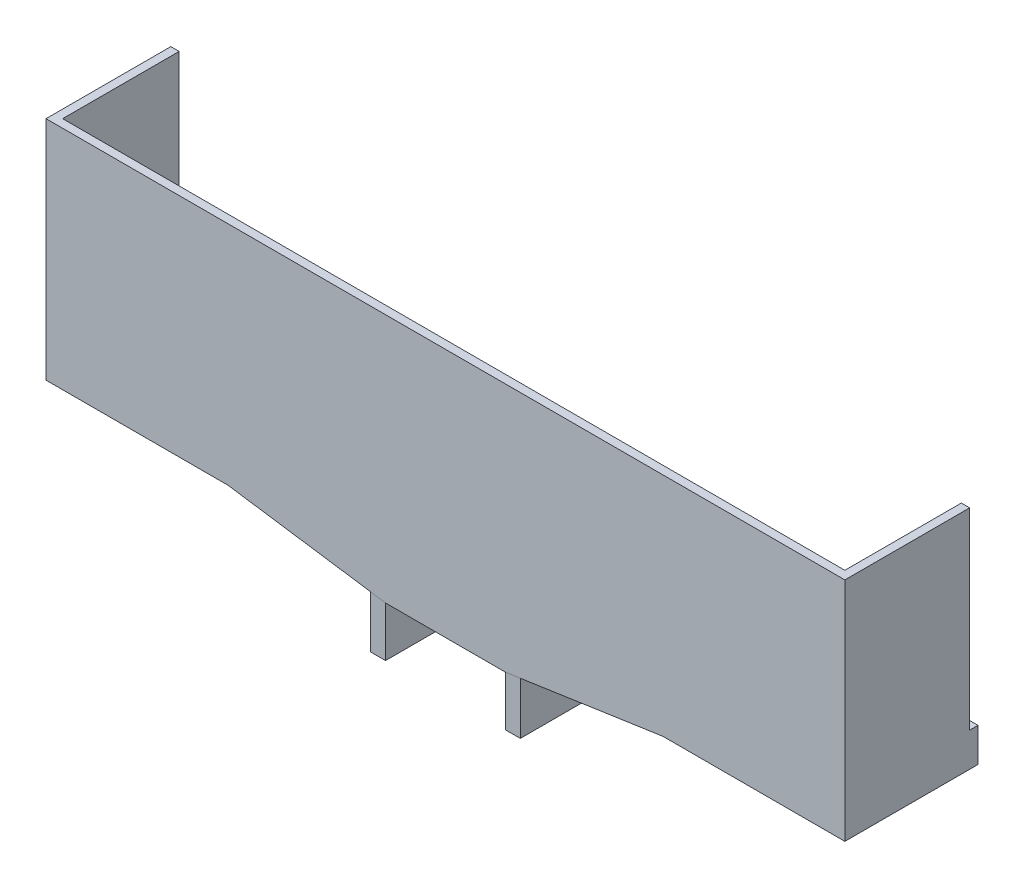
SolidWorks part; units mm, degrees
ref_plane "前基準面" through (0, 0, 0) normal (0, 0, 1) x (1, 0, 0)
ref_plane "上基準面" through (0, 0, 0) normal (0, 1, 0) x (1, 0, 0)
ref_plane "右基準面" through (0, 0, 0) normal (1, 0, 0) x (0, 0, -1)
sketch "草圖20" plane through (0, 0, 0) normal (0, 0, 1) x (1, 0, 0)
  line L0 (-36, 0) -> (36, 0) construction
  line L1 (-36, 0) -> (-240, 30)
  line L2 (-240, 30) -> (240, 30) construction
  line L3 (240, 30) -> (36, 0)
  line L4 (36, 0) -> (-36, 0)
  line L5 (0, 89.4424) -> (0, -40.7257) construction
  line L7 (-240, 30) -> (240, 30) construction
  line L8 (-240, 30) -> (-240, 150)
  line L9 (-240, 150) -> (240, 150)
  line L10 (240, 30) -> (240, 150)
  point P2 (0, 0)
  dimension "D1" = 72
  dimension "D2" = 480
  dimension "D3" = 30
  dimension "D4" = 120
extrude "填料-伸長1" add sketch "草圖20" along normal blind 80
ref_plane "平面1" through (0, 0, 5) normal (0, 0, 1) x (1, 0, 0)
sketch "草圖22" plane through (0, 0, 5) normal (0, 0, 1) x (1, 0, 0)
  line L6 (-235, 34.3185) -> (-35.6343, 5)
  line L7 (-235, 34.3185) -> (-36, 5.0538)
  line L8 (35.6343, 5) -> (235, 34.3185)
  line L9 (36, 5.0538) -> (235, 34.3185)
  line L332 (36, 0) -> (36, 5.0538)
  line L333 (-36, 0) -> (-36, 5.0538)
  line L334 (-36, 0) -> (36, 0) construction
  line L335 (-36, 0) -> (36, 0)
  line L336 (240, 150) -> (-240, 150) construction
  line L337 (235, 150) -> (-235, 150)
  line L338 (-35.6343, 5) -> (35.6343, 5)
  line L340 (-235, 145) -> (-235, 34.3185)
  line L341 (235, 145) -> (-235, 145)
  line L342 (235, 34.3185) -> (235, 145)
  line L346 (-235, 150) -> (-235, 34.3185)
  line L348 (235, 34.3185) -> (235, 150)
  dimension "D1" = 5
extrude "除料-伸長1" cut sketch "草圖22" along normal blind 70
sketch "草圖23" plane through (0, 0, 0) normal (0, 0, -1) x (-1, 0, 0)
  line L0 (-240, 34.3185) -> (-235, 34.3185)
  line L1 (-240, 150) -> (240, 150)
  line L2 (-240, 150) -> (-240, 34.3185)
  line L4 (240, 150) -> (240, 34.3185)
  line L5 (240, 150) -> (240, 30) construction
  line L6 (235, 34.3185) -> (36, 5.0538) construction
  line L7 (-36, 5.0538) -> (-235, 34.3185) construction
  line L8 (235, 34.3185) -> (36, 5.0538)
  line L9 (-36, 5.0538) -> (-235, 34.3185)
  line L10 (235, 34.3185) -> (240, 34.3185)
  line L15 (-36, 0) -> (36, 0)
  line L16 (-36, 5.0538) -> (-36, 0)
  line L17 (-235, 34.3185) -> (-36, 5.0538)
  line L18 (-235, 150) -> (-235, 34.3185)
  line L19 (235, 150) -> (-235, 150)
  line L20 (235, 34.3185) -> (235, 150)
  line L21 (36, 5.0538) -> (235, 34.3185)
  line L22 (36, 0) -> (36, 5.0538)
  line L23 (-36, 0) -> (36, 0)
  line L24 (-36, 5.0538) -> (-36, 0)
  line L25 (-235, 34.3185) -> (-36, 5.0538) construction
  line L26 (-235, 150) -> (-235, 34.3185) construction
  line L27 (235, 150) -> (-235, 150) construction
  line L28 (235, 34.3185) -> (235, 150) construction
  line L29 (36, 5.0538) -> (235, 34.3185) construction
  line L30 (36, 0) -> (36, 5.0538)
  dimension "D1" = 0
extrude "除料-伸長2" cut sketch "草圖23" against normal up to surface (5 mm away) up to face at (0, 47.3431, 5)
sketch "草圖25" plane through (0, 0, 0) normal (0, -1, 0) x (1, 0, 0)
  line L0 (-240, 80) -> (-36, 80) construction
  line L1 (-45, 80) -> (-36, 80)
  line L2 (-45, 80) -> (-45, 40)
  line L3 (-45, 40) -> (-36, 40)
  line L4 (45, 80) -> (45, 40)
  line L8 (-36, 75) -> (-36, 0) construction
  line L9 (-36, 75) -> (-36, 0)
  line L10 (36, 75) -> (36, 0) construction
  line L11 (36, 75) -> (36, 0)
  line L14 (0, 112.0403) -> (0, -32.5908) construction
  line L15 (-36, 80) -> (-36, 40)
  line L16 (36, 80) -> (45, 80)
  line L17 (36, 80) -> (36, 40)
  line L18 (36, 40) -> (45, 40)
  point P20 (0, 0)
  point P22 (0, 0)
  point P25 (0, 0)
  point P26 (0, 0)
  line M10 (-36, 80) -> (-36, 75)
  line M12 (36, 75) -> (36, 80)
  dimension "D1" = 90
  dimension "D2" = 40
extrude "填料-伸長3" add sketch "草圖25" along normal blind 30 and the other way up to next separate body contours L15 L9 L1 L2 L3 M10 | L17 L18 L4 L16 L11 M12 region at (-40.5, 0, 60) region at (40.5, 0, 60)
sketch "草圖26" plane through (0, 0, 0) normal (0, 0, -1) x (-1, 0, 0)
  line L0 (-130.69, 13.925) -> (-240, 13.925)
  line L1 (-36, 0) -> (-240, 30) construction
  line L2 (-240, 13.925) -> (-240, 30)
  line L3 (-240, 30) -> (-130.69, 13.925)
  line L5 (0, 209.7105) -> (0, -36.6515) construction
  line L6 (240, 13.925) -> (240, 30)
  line L7 (130.69, 13.925) -> (240, 13.925)
  line L8 (240, 30) -> (130.69, 13.925)
  dimension "D1" = 109.31
  dimension "D2" = 16.075
extrude "填料-伸長4" add sketch "草圖26" against normal up to surface (80 mm away) up to face at (0, 60, 80)
chamfer "導角1" distance 3 angle 45 2 edges at (-36, 5.0538, 37.5) (36, 5.0538, 37.5) first distance on face at (-36, 2.5269, 37.5) first distance on face at (155.4, 22.6126, 31)
